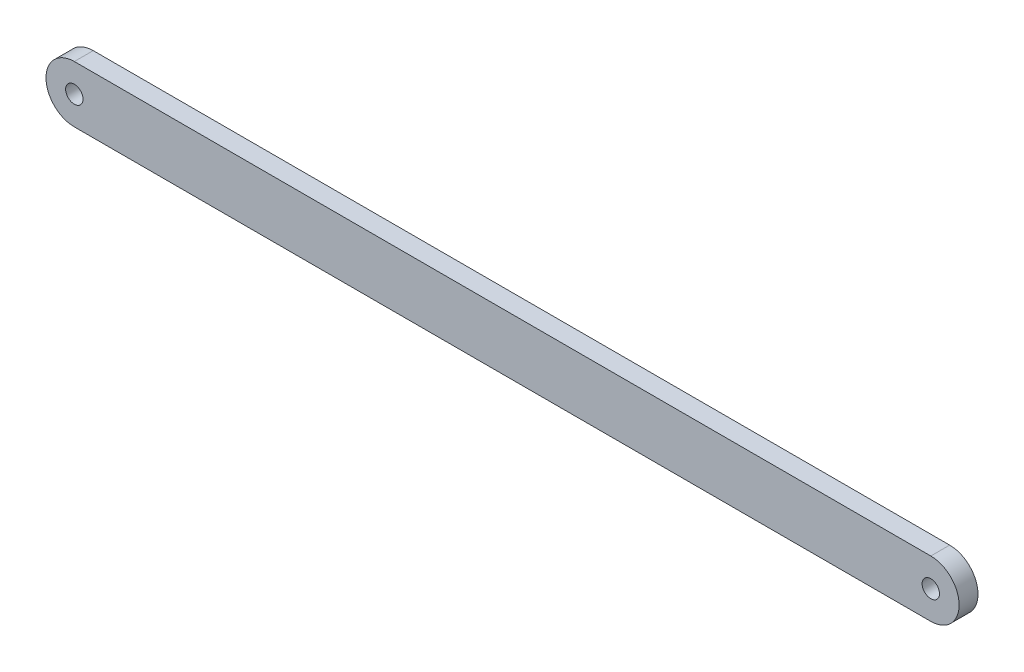
SolidWorks part; units mm, degrees
ref_plane "前视基准面" through (0, 0, 0) normal (0, 0, 1) x (1, 0, 0)
ref_plane "上视基准面" through (0, 0, 0) normal (0, 1, 0) x (1, 0, 0)
ref_plane "右视基准面" through (0, 0, 0) normal (1, 0, 0) x (0, 0, -1)
other "Configuration Table"
sketch "草图1" plane through (0, 0, 0) normal (0, 0, 1) x (1, 0, 0)
  line L1 (-113.4, 7.5) -> (113.4, 7.5)
  line L3 (-113.4, -7.5) -> (113.4, -7.5)
  line L5 (-113.4, 7.5) -> (113.4, -7.5) construction
  line L6 (-113.4, -7.5) -> (113.4, 7.5) construction
  arc A0 (-113.4, 7.5) -> (-113.4, -7.5) centre (-113.4, 0) ccw
  arc A1 (113.4, 7.5) -> (113.4, -7.5) centre (113.4, 0) cw
  circle A2 centre (-113.4, 0) radius 2.3
  circle A3 centre (113.4, 0) radius 2.3
  point P0 (0, 0)
  dimension "D1" = 4.6
  dimension "D2" = 4.6
  dimension "D3" = 226.8
  dimension "D4" = 15
extrude "凸台-拉伸1" add sketch "草图1" along normal blind 5
equation "\"fi\"=4.6"
equation "\"D1@草图1\"=\"fi\""
equation "\"D2@草图1\"=\"fi\""
equation "\"b0\"=75.6"
equation "\"D3@草图1\"=\"b2\""
equation "\"width\"=15"
equation "\"D4@草图1\"=\"width\""
equation "\"depth\"=5"
equation "\"D1@凸台-拉伸1\"=\"depth\""
equation "\"b1\"= \"b0\" * 3 / 2"
equation "\"b2\"= \"b0\" * 6 / 2"
equation "\"b3\"= \"b0\" * 4 / 2"
equation "\"b4\"= \"b0\" * 7 / 2"
equation "\"angle\"= 90度"
